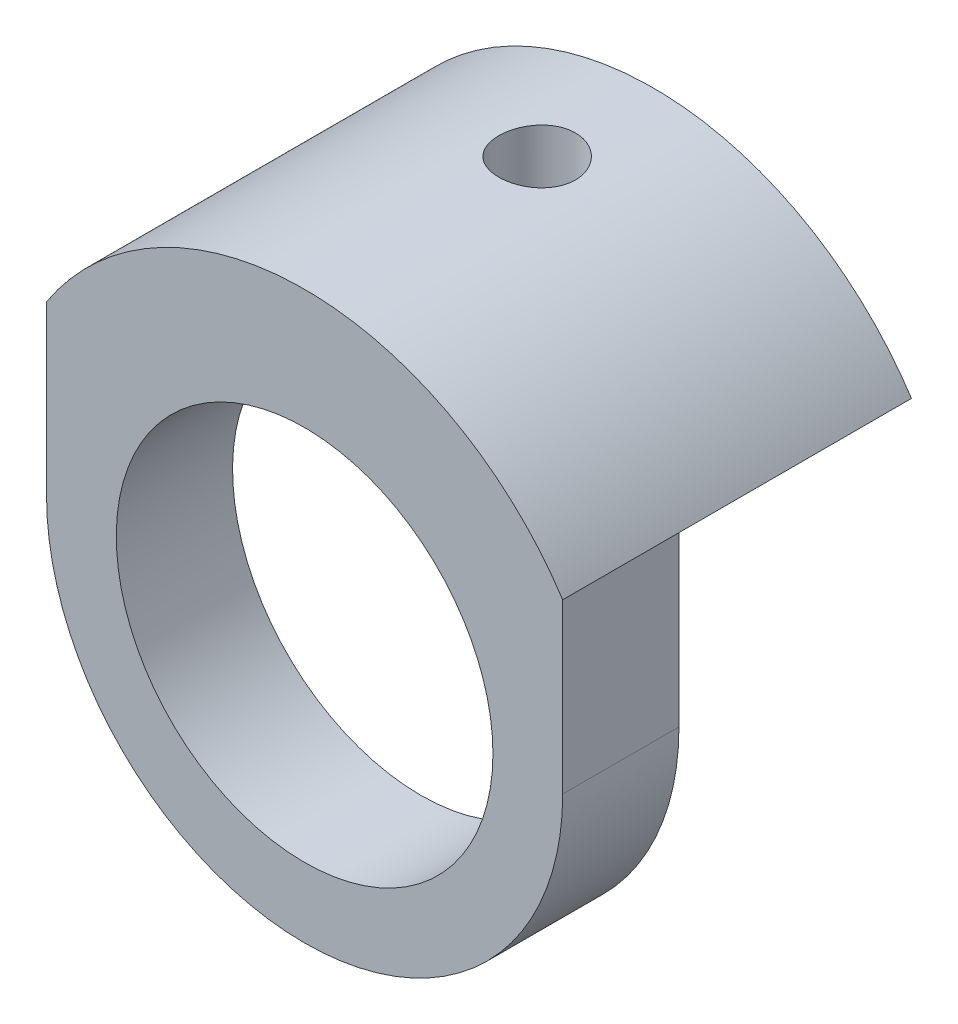
SolidWorks part; units mm, degrees
ref_plane "Front Plane" through (0, 0, 0) normal (0, 0, 1) x (1, 0, 0)
ref_plane "Top Plane" through (0, 0, 0) normal (0, 1, 0) x (1, 0, 0)
ref_plane "Right Plane" through (0, 0, 0) normal (1, 0, 0) x (0, 0, -1)
sketch "Sketch1" plane through (0, 0, 0) normal (0, 0, 1) x (1, 0, 0)
  line L0 (-11.1, 0) -> (11.1, 0)
  line L1 (-11.1, 0) -> (-11.1, 7.2355)
  line L2 (11.1, 0) -> (11.1, 7.2355)
  circle A0 centre (0, 0) radius 8.1
  circle A1 centre (0, 0) radius 13.25
  circle A2 centre (0, 0) radius 11.1
  dimension "16.2" = 16.2
  dimension "D2" = 26.5
  dimension "D3" = 3
extrude "Boss-Extrude1" add sketch "Sketch1" along normal blind 15 contours L0 A2 A0 | A2 L2 A1 L1 | L0 A2 A0 region at (0, 8.3482, 0) region at (9.6, -0.2482, 0) region at (0, 11.3585, 0)
sketch "Sketch2" plane through (-11.1, 0, 0) normal (-1, 0, 0) x (0, 0, 1)
  line L0 (15, 0) -> (15, 7.2355) construction
  line L1 (0, 7.2355) -> (10, 7.2355)
  line L2 (0, 7.2355) -> (0, -11.1)
  line L3 (0, -11.1) -> (10, -11.1)
  line L4 (10, 7.2355) -> (10, -11.1)
  dimension "D1" = 5
extrude "Cut-Extrude1" cut sketch "Sketch2" against normal up to surface (22.2 mm away) up to face at (11.1, 3.6178, 7.5)
sketch "Sketch3" plane through (0, 7.2355, 0) normal (0, -1, 0) x (1, 0, 0)
  line L0 (-3.6411, 0) -> (3.6411, 0) construction
  circle A0 centre (0, 5) radius 1.65
  dimension "D1" = 3.3
  dimension "D2" = 5
extrude "Cut-Extrude2" cut sketch "Sketch3" against normal up to surface (5.9114 mm away) up to face at (0, 9.2403, 8.3333)
sketch "Sketch4" plane through (0, 7.2355, 0) normal (0, -1, 0) x (1, 0, 0)
  line L0 (-3.6411, 0) -> (3.6411, 0) construction
  line L1 (1.6166, 7.8) -> (-1.6166, 7.8)
  line L2 (-1.6166, 7.8) -> (-3.2332, 5)
  line L3 (-3.2332, 5) -> (-1.6166, 2.2)
  line L4 (-1.6166, 2.2) -> (1.6166, 2.2)
  line L5 (1.6166, 2.2) -> (3.2332, 5)
  line L6 (3.2332, 5) -> (1.6166, 7.8)
  circle A0 centre (0, 5) radius 2.8 construction
  dimension "D1" = 5.6
extrude "Cut-Extrude3" cut sketch "Sketch4" against normal blind 3
